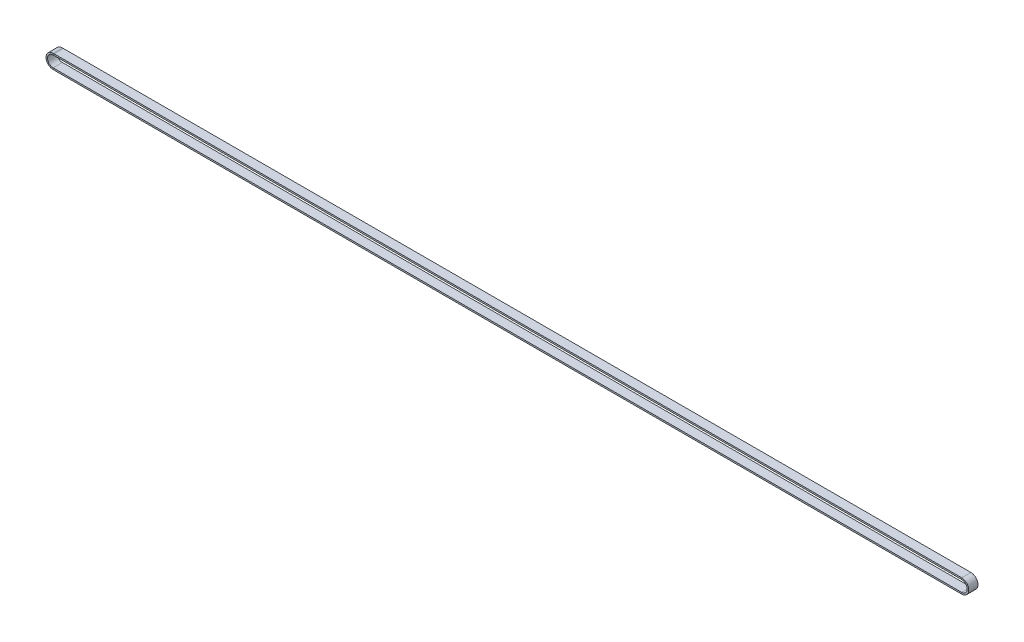
SolidWorks part; units mm, degrees
ref_plane "Front Plane" through (0, 0, 0) normal (0, 0, 1) x (1, 0, 0)
ref_plane "Top Plane" through (0, 0, 0) normal (0, 1, 0) x (1, 0, 0)
ref_plane "Right Plane" through (0, 0, 0) normal (1, 0, 0) x (0, 0, -1)
sketch "Sketch2" plane through (0, 0, -133.7334) normal (0, 0, 1) x (1, 0, 0)
  line L0 (0, 0) -> (1, 0) construction
  line L1 (0, 0) -> (0, 1) construction
  line L2 (-1, 148.3793) -> (883.5206, 148.3793)
  line L3 (883.5206, 134.5793) -> (-1, 134.5793)
  arc A0 (-1, 134.5793) -> (-1, 148.3793) centre (-1, 141.4793) cw
  arc A1 (883.5206, 148.3793) -> (883.5206, 134.5793) centre (883.5206, 141.4793) cw
sketch "Sketch3" plane through (0, 0, 0) normal (1, 0, 0) x (0, 0, -1)
  line L1 (133.7334, 146.8793) -> (124.7334, 146.8793)
  line L2 (133.7334, 146.8793) -> (133.7334, 148.3793)
  line L3 (133.7334, 148.3793) -> (124.7334, 148.3793)
  line L4 (124.7334, 146.8793) -> (124.7334, 148.3793)
  dimension "D1" = 9
  dimension "D2" = 1.5
sweep "Sweep1" add profiles "Sketch3" path "Sketch2"
